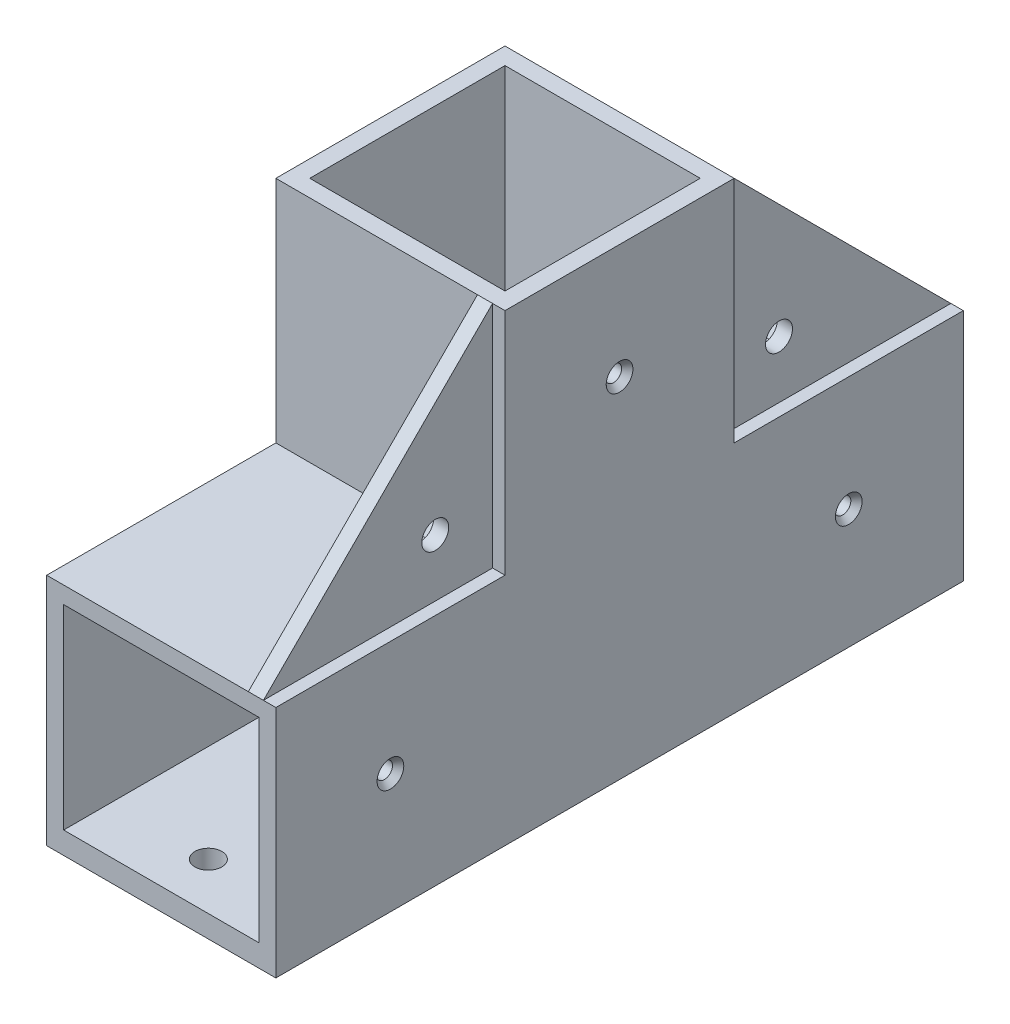
SolidWorks part; units mm, degrees
ref_plane "Plan de face" through (0, 0, 0) normal (0, 0, 1) x (1, 0, 0)
ref_plane "Plan de dessus" through (0, 0, 0) normal (0, 1, 0) x (1, 0, 0)
ref_plane "Plan de droite" through (0, 0, 0) normal (1, 0, 0) x (0, 0, -1)
sketch "Esquisse1" plane through (0, 0, 0) normal (0, 0, 1) x (1, 0, 0)
  line L0 (-30.4, 60.8) -> (30.4, -60.8) construction
  line L1 (-30.4, 60.8) -> (30.4, 60.8)
  line L2 (-30.4, 60.8) -> (-30.4, -60.8)
  line L3 (-30.4, -60.8) -> (30.4, -60.8)
  line L4 (30.4, 60.8) -> (30.4, -60.8)
  line L5 (-30.4, -60.8) -> (30.4, 60.8) construction
  point P4 (0, 0)
  dimension "D1" = 121.6
  dimension "D2" = 60.8
extrude "Boss.-Extru.1" add sketch "Esquisse1" along normal mid plane 182.4 contours L2 L3 L4 L1
sketch "Esquisse2" plane through (-30.4, 0, 0) normal (-1, 0, 0) x (0, 0, 1)
  line L1 (-91.2, 60.8) -> (-30.4, 60.8)
  line L2 (-91.2, 60.8) -> (-91.2, 0)
  line L3 (-91.2, 0) -> (-30.4, 0)
  line L4 (-30.4, 60.8) -> (-30.4, 0)
  dimension "D1" = 60.8
extrude "Enlèv. mat.-Extru.1" cut sketch "Esquisse2" against normal through all
sketch "Esquisse3" plane through (0, 0, -91.2) normal (0, 0, -1) x (-1, 0, 0)
  line L0 (-25.9, -4.5) -> (25.9, -56.3) construction
  line L1 (-25.9, -4.5) -> (25.9, -4.5)
  line L2 (-25.9, -4.5) -> (-25.9, -56.3)
  line L3 (-25.9, -56.3) -> (25.9, -56.3)
  line L4 (25.9, -4.5) -> (25.9, -56.3)
  line L5 (-25.9, -56.3) -> (25.9, -4.5) construction
  line L6 (30.4, 0) -> (30.4, -60.8) construction
  point P4 (0, -30.4)
  point P8 (30.4, -30.4)
  dimension "D1" = 51.8
extrude "Enlèv. mat.-Extru.2" cut sketch "Esquisse3" against normal blind 60.8
mirror "Symétrie2" about plane through (0, 0, 0) normal (0, 0, 1) of "Enlèv. mat.-Extru.2", "Enlèv. mat.-Extru.1"
ref_plane "Plan2" [suppressed] through (25.4, 0, 0) normal (1, 0, 0) x (0, 0, -1)
ref_plane "Plan1" through (27.1, 0, 0) normal (1, 0, 0) x (0, 0, -1)
sketch "Esquisse10" plane through (27.1, 0, 0) normal (1, 0, 0) x (0, 0, -1)
  line L0 (91.2, 0) -> (91.2, -60.8) construction
  line L2 (30.4, 60.8) -> (30.4, 0)
  line L3 (30.4, 0) -> (91.2, 0)
  line L5 (91.2, 0) -> (30.4, 0) construction
  line L6 (30.4, 60.8) -> (91.2, 0)
  line L7 (-30.4, 60.8) -> (-91.2, 0)
  line L8 (-91.2, 0) -> (-30.4, 0)
  line L9 (-30.4, 0) -> (-30.4, 60.8)
  dimension "D1" = 3.3
extrude "Boss.-Extru.3" add sketch "Esquisse10" against normal blind 4
sketch "Esquisse6" plane through (0, 60.8, 0) normal (0, 1, 0) x (1, 0, 0)
  line L0 (-25.9, 25.9) -> (25.9, -25.9) construction
  line L1 (-25.9, 25.9) -> (25.9, 25.9)
  line L2 (-25.9, 25.9) -> (-25.9, -25.9)
  line L3 (-25.9, -25.9) -> (25.9, -25.9)
  line L4 (25.9, 25.9) -> (25.9, -25.9)
  line L5 (-25.9, -25.9) -> (25.9, 25.9) construction
  point P4 (0, 0)
  dimension "D1" = 51.8
extrude "Enlèv. mat.-Extru.3" cut sketch "Esquisse6" against normal blind 60.8
sketch "Esquisse16" plane through (30.4, 0, 0) normal (1, 0, 0) x (0, 0, -1)
  line L8 (-30.4, 60.8) -> (-30.4, 0)
  line L9 (-30.4, 0) -> (-91.2, 0)
  line L10 (-91.2, 0) -> (-91.2, -60.8)
  line L11 (-91.2, -60.8) -> (91.2, -60.8)
  line L12 (91.2, -60.8) -> (91.2, 0)
  line L13 (91.2, 0) -> (30.4, 0)
  line L14 (30.4, 0) -> (30.4, 60.8)
  line L15 (30.4, 60.8) -> (-30.4, 60.8)
  line L16 (-30.4, 60.8) -> (-30.4, 0)
  line L17 (-30.4, 0) -> (-91.2, 0)
  line L18 (-91.2, 0) -> (-91.2, -60.8)
  line L19 (-91.2, -60.8) -> (91.2, -60.8)
  line L20 (91.2, -60.8) -> (91.2, 0)
  line L21 (91.2, 0) -> (30.4, 0)
  line L22 (30.4, 0) -> (30.4, 60.8)
  line L23 (30.4, 60.8) -> (-30.4, 60.8)
  dimension "D1" = 0
extrude "Boss.-Extru.4" [suppressed] add sketch "Esquisse16" along normal blind 1.35
hole_wizard "Dégagement 1/41" [suppressed] positions "Esquisse4" profile "Esquisse5" hole size "1/4" standard "Ansi Inch"
sketch "Esquisse4" [suppressed] plane through (25.4, 0, 0) normal (1, 0, 0) x (0, 0, -1)
  line L4 (60.8, 30.4) -> (30.4, 0) construction
  line L5 (91.2, 0) -> (30.4, 60.8) construction
  line L6 (-30.4, 0) -> (-60.8, 30.4) construction
  line L7 (-30.4, 60.8) -> (-91.2, 0) construction
  point P11 (45.6, 15.2)
  point P33 (45.6, 15.2)
  point P41 (-45.6, 15.2)
sketch "Esquisse5" plane through (25.4, 15.2, -45.6) normal (0, 1, 0) x (0, 0, -1)
  line L0 (0, 0) -> (0, 20)
  line L1 (0, 20) -> (3.3782, 20)
  line L2 (3.3782, 20) -> (3.3782, 0)
  line L5 (3.3782, 0) -> (0, 0)
  line L10 (0, 20) -> (-3.3782, 20) construction
  line L11 (0, -6.35) -> (0, 107.95) construction
  dimension "Diamètre du perçage" = 6.7564
  dimension "Profondeur du perçage" = 20
  dimension "Angle de pointe" = 180
hole_wizard "Fraisage pour vis à tête fraisée bombée #61" [suppressed] positions "Esquisse11" profile "Esquisse12" countersink size "#6" standard "Ansi Inch"
sketch "Esquisse11" [suppressed] plane through (31.75, 0, 0) normal (1, 0, 0) x (0, 0, -1)
  line L2 (-30.4, 30.4) -> (30.4, 30.4) construction
  line L3 (-30.4, 0) -> (-30.4, 60.8) construction
  line L6 (0, 0) -> (0, -10.6338) construction
  line L8 (30.4, 60.8) -> (30.4, 0) construction
  line L9 (60.8, 0) -> (60.8, -60.8) construction
  line L10 (91.2, 0) -> (30.4, 0) construction
  line L11 (-91.2, -60.8) -> (91.2, -60.8) construction
  point P0 (60.8, -30.4)
  point P22 (-60.8, -30.4)
  point P23 (0, 30.4)
  point P39 (60.8, -30.4)
sketch "Esquisse12" plane through (31.75, -30.4, -60.8) normal (0, 1, 0) x (0, 0, -1)
  line L0 (0, 0) -> (0, 20)
  line L1 (0, 20) -> (2.1526, 20)
  line L2 (2.1526, 20) -> (2.1526, 1.5998)
  line L3 (2.1526, 1.5998) -> (3.5433, 0)
  line L5 (3.5433, 0) -> (0, 0)
  line L6 (-2.1526, 1.5998) -> (-3.5433, 0) construction
  line L10 (0, 20) -> (-2.1527, 20) construction
  line L11 (0, -6.35) -> (0, 107.95) construction
  dimension "Diamètre du perçage" = 4.3053
  dimension "Profondeur du perçage" = 20
  dimension "Diamètre du fraisage entrant" = 7.0866
  dimension "Angle du fraisage entrant" = 82
  dimension "Angle de pointe" = 180
hole_wizard "Dégagement 1/43" positions "Esquisse17" profile "Esquisse19" hole size "1/4" standard "Ansi Inch" end condition through all
sketch "Esquisse17" plane through (27.1, 0, 0) normal (1, 0, 0) x (0, 0, -1)
  line L0 (-60.8, 30.4) -> (-30.4, 0) construction
  line L1 (-30.4, 60.8) -> (-91.2, 0) construction
  line L3 (60.8, 30.4) -> (30.4, 0) construction
  line L4 (91.2, 0) -> (30.4, 60.8) construction
  point P15 (-45.6, 15.2)
  point P17 (45.6, 15.2)
sketch "Esquisse19" plane through (27.1, 15.2, -45.6) normal (0, 1, 0) x (0, 0, -1)
  line L0 (0, 0) -> (0, 57.5)
  line L1 (0, 57.5) -> (3.5712, 57.5)
  line L2 (3.5712, 57.5) -> (3.5712, 0)
  line L5 (3.5712, 0) -> (0, 0)
  line L11 (0, -6.35) -> (0, 107.95) construction
  dimension "Diamètre du perçage jusqu'au prochain" = 7.1425
  dimension "Profondeur du perçage jusqu'au prochain" = 57.5
hole_wizard "Fraisage pour vis à tête fraisée bombée #62" positions "Esquisse22" profile "Esquisse21" countersink size "#6" standard "Ansi Inch" end condition up to next
sketch "Esquisse22" plane through (30.4, 0, 0) normal (1, 0, 0) x (0, 0, -1)
  line L0 (-60.8, 0) -> (-60.8, -60.8) construction
  line L1 (-91.2, 0) -> (-30.4, 0) construction
  line L2 (-91.2, -60.8) -> (91.2, -60.8) construction
  line L4 (-30.4, 30.4) -> (30.4, 30.4) construction
  line L5 (-30.4, 0) -> (-30.4, 60.8) construction
  line L6 (30.4, 0) -> (30.4, 60.8) construction
  line L8 (60.8, 0) -> (60.8, -60.8) construction
  line L9 (91.2, 0) -> (30.4, 0) construction
  point P0 (-60.8, -30.4)
  point P23 (0, 30.4)
  point P25 (60.8, -30.4)
sketch "Esquisse21" plane through (30.4, -30.4, 60.8) normal (0, 1, 0) x (0, 0, -1)
  line L0 (0, 0) -> (0, 4.5)
  line L1 (0, 4.5) -> (2.1526, 4.5)
  line L2 (2.1526, 4.5) -> (2.1526, 1.5998)
  line L3 (2.1526, 1.5998) -> (3.5433, 0)
  line L5 (3.5433, 0) -> (0, 0)
  line L6 (-2.1526, 1.5998) -> (-3.5433, 0) construction
  line L11 (0, -6.35) -> (0, 107.95) construction
  dimension "Diamètre du perçage jusqu'au prochain" = 4.3053
  dimension "Profondeur du perçage jusqu'au prochain" = 4.5
  dimension "Diamètre du fraisage entrant" = 7.0866
  dimension "Angle du fraisage entrant" = 82
hole_wizard "Dégagement 1/42" positions "Esquisse14" profile "Esquisse15" hole size "1/4" standard "Ansi Inch"
sketch "Esquisse14" plane through (0, -60.8, 0) normal (0, -1, 0) x (-1, 0, 0)
  point P13 (0, 78.7)
  point P15 (0, -78.7)
  dimension "D2" = 78.7
  dimension "D3" = 78.7
sketch "Esquisse15" plane through (0, -60.8, -78.7) normal (1, 0, 0) x (0, 0, -1)
  line L0 (0, 0) -> (0, 20)
  line L1 (0, 20) -> (3.5712, 20)
  line L2 (3.5712, 20) -> (3.5712, 0)
  line L5 (3.5712, 0) -> (0, 0)
  line L10 (0, 20) -> (-3.5712, 20) construction
  line L11 (0, -6.35) -> (0, 107.95) construction
  dimension "Diamètre du perçage" = 7.1425
  dimension "Profondeur du perçage" = 20
  dimension "Angle de pointe" = 180
sketch "Esquisse23" plane through (23.1, 0, 0) normal (-1, 0, 0) x (0, 0, 1)
  line L0 (-41.1977, 22.825) -> (-50.0023, 22.825)
  line L1 (-40.2595, 15.2) -> (-42.9298, 19.825)
  line L2 (-42.9298, 19.825) -> (-48.2702, 19.825)
  line L3 (-48.2702, 19.825) -> (-50.9405, 15.2)
  line L4 (-50.9405, 15.2) -> (-48.2702, 10.575)
  line L5 (-48.2702, 10.575) -> (-42.9298, 10.575)
  line L6 (-42.9298, 10.575) -> (-40.2595, 15.2)
  line L7 (50.9405, 15.2) -> (48.2702, 19.825)
  line L8 (48.2702, 19.825) -> (42.9298, 19.825)
  line L9 (42.9298, 19.825) -> (40.2595, 15.2)
  line L10 (40.2595, 15.2) -> (42.9298, 10.575)
  line L11 (42.9298, 10.575) -> (48.2702, 10.575)
  line L12 (48.2702, 10.575) -> (50.9405, 15.2)
  line L13 (-50.0023, 22.825) -> (-54.4046, 15.2)
  line L14 (-54.4046, 15.2) -> (-50.0023, 7.575)
  line L15 (-50.0023, 7.575) -> (-41.1977, 7.575)
  line L16 (-41.1977, 7.575) -> (-36.7954, 15.2)
  line L17 (-36.7954, 15.2) -> (-41.1977, 22.825)
  line L18 (54.4046, 15.2) -> (50.0023, 22.825)
  line L19 (50.0023, 22.825) -> (41.1977, 22.825)
  line L20 (41.1977, 22.825) -> (36.7954, 15.2)
  line L21 (36.7954, 15.2) -> (41.1977, 7.575)
  line L22 (41.1977, 7.575) -> (50.0023, 7.575)
  line L23 (50.0023, 7.575) -> (54.4046, 15.2)
  circle A0 centre (-45.6, 15.2) radius 4.625 construction
  circle A1 centre (45.6, 15.2) radius 4.625 construction
  dimension "D1" = 9.25
  dimension "D2" = 3
  dimension "D3" = 3
extrude "Boss.-Extru.5" add sketch "Esquisse23" along normal blind 4
chamfer "Chanfrein1" distance 4 angle 45 12 edges at (23.1, 19.0125, 38.9966) (23.1, 11.3875, 38.9966) (23.1, 7.575, 45.6) (23.1, 11.3875, 52.2034) (23.1, 19.0125, 52.2034) (23.1, 22.825, 45.6) (23.1, 11.3875, -38.9966) (23.1, 19.0125, -38.9966) (23.1, 7.575, -45.6) (23.1, 11.3875, -52.2034) (23.1, 22.825, -45.6) (23.1, 19.0125, -52.2034)
sketch "Esquisse25" [suppressed] plane through (21.4, 0, 0) normal (-1, 0, 0) x (0, 0, 1)
  line L0 (-36.7954, 15.2) -> (-41.1977, 22.825)
  line L1 (-40.2595, 15.2) -> (-42.9298, 19.825)
  line L2 (-42.9298, 19.825) -> (-48.2702, 19.825)
  line L3 (-48.2702, 19.825) -> (-50.9405, 15.2)
  line L4 (-50.9405, 15.2) -> (-48.2702, 10.575)
  line L5 (-48.2702, 10.575) -> (-42.9298, 10.575)
  line L6 (-42.9298, 10.575) -> (-40.2595, 15.2)
  line L7 (50.9405, 15.2) -> (48.2702, 19.825)
  line L8 (48.2702, 19.825) -> (42.9298, 19.825)
  line L9 (42.9298, 19.825) -> (40.2595, 15.2)
  line L10 (40.2595, 15.2) -> (42.9298, 10.575)
  line L11 (42.9298, 10.575) -> (48.2702, 10.575)
  line L12 (48.2702, 10.575) -> (50.9405, 15.2)
  line L13 (-41.1977, 22.825) -> (-50.0023, 22.825)
  line L14 (-50.0023, 22.825) -> (-54.4046, 15.2)
  line L15 (-54.4046, 15.2) -> (-50.0023, 7.575)
  line L16 (-50.0023, 7.575) -> (-41.1977, 7.575)
  line L17 (-41.1977, 7.575) -> (-36.7954, 15.2)
  line L18 (50.0023, 22.825) -> (41.1977, 22.825)
  line L19 (41.1977, 22.825) -> (36.7954, 15.2)
  line L20 (36.7954, 15.2) -> (41.1977, 7.575)
  line L21 (41.1977, 7.575) -> (50.0023, 7.575)
  line L22 (50.0023, 7.575) -> (54.4046, 15.2)
  line L23 (54.4046, 15.2) -> (50.0023, 22.825)
  circle A0 centre (-45.6, 15.2) radius 4.625 construction
  circle A1 centre (45.6, 15.2) radius 4.625 construction
  dimension "D1" = 9.25
  dimension "D2" = 3
extrude "Boss.-Extru.6" [suppressed] add sketch "Esquisse25" along normal blind 4
chamfer "Chanfrein2" [suppressed] distance 4 angle 45
sketch "Esquisse26" plane through (0, -60.8, 0) normal (0, -1, 0) x (1, 0, 0)
  line L4 (-30.4, -91.2) -> (30.4, -91.2)
  line L5 (30.4, -91.2) -> (30.4, 91.2)
  line L6 (30.4, 91.2) -> (-30.4, 91.2)
  line L7 (-30.4, 91.2) -> (-30.4, -91.2)
  line L8 (-30.4, -91.2) -> (30.4, -91.2)
  line L10 (30.4, 91.2) -> (-30.4, 91.2)
  line L11 (-30.4, 91.2) -> (-30.4, -91.2)
  line L12 (30.4, -91.2) -> (30.4, 91.2)
  circle A1 centre (0, 78.7) radius 3.5712
  circle A2 centre (0, 78.7) radius 3.5712
  circle A3 centre (0, -78.7) radius 3.5712
  circle A4 centre (0, -78.7) radius 3.5712
  dimension "D1" = 0
  dimension "D2" = 0
  dimension "D3" = 0
extrude "Boss.-Extru.7" add sketch "Esquisse26" along normal blind 1.35
